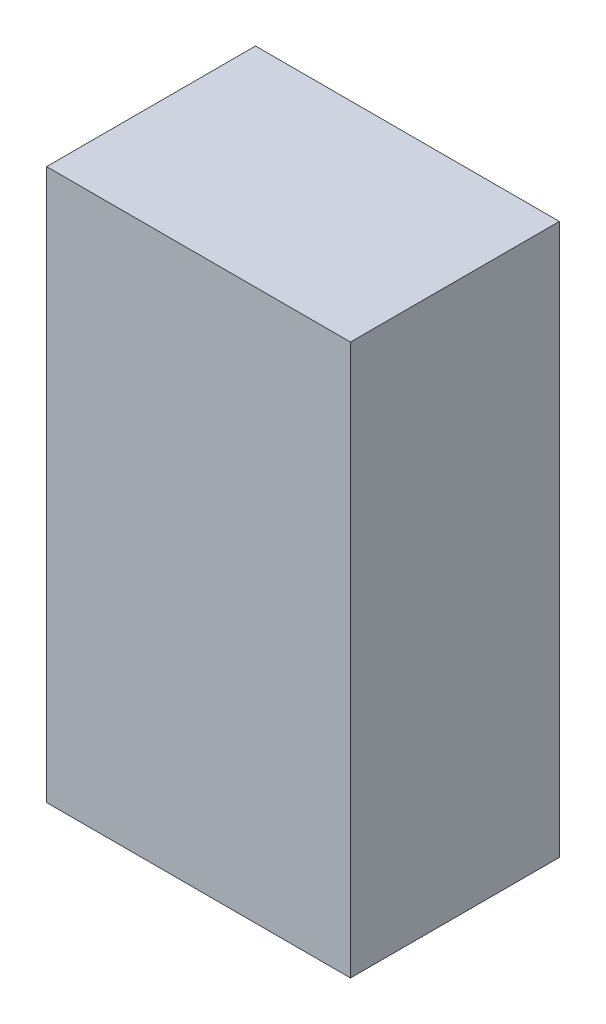
SolidWorks part; units mm, degrees
material "Custom Plastic"
ref_plane "X-Y Datum" through (0, 0, 0) normal (0, 0, 1) x (1, 0, 0)
ref_plane "X-Z Datum" through (0, 0, 0) normal (0, 1, 0) x (1, 0, 0)
ref_plane "Y-Z Datum" through (0, 0, 0) normal (1, 0, 0) x (0, 0, -1)
sketch "Sketch1" plane through (0, 0, 0) normal (0, 1, 0) x (1, 0, 0)
  line L1 (0, 0) -> (50.8, 0)
  line L2 (0, 0) -> (0, 34.925)
  line L3 (0, 34.925) -> (50.8, 34.925)
  line L4 (50.8, 0) -> (50.8, 34.925)
  dimension "D1" = 50.8
  dimension "D2" = 34.925
extrude "Boss-Extrude1" add sketch "Sketch1" along normal blind 92.075
sketch "Sketch2" plane through (0, 0, -34.925) normal (0, 0, -1) x (-1, 0, 0)
  line L0 (-50.8, 46.0375) -> (0, 46.0375) construction
  line L1 (-50.8, 92.075) -> (-50.8, 0) construction
  line L2 (0, 92.075) -> (0, 0) construction
